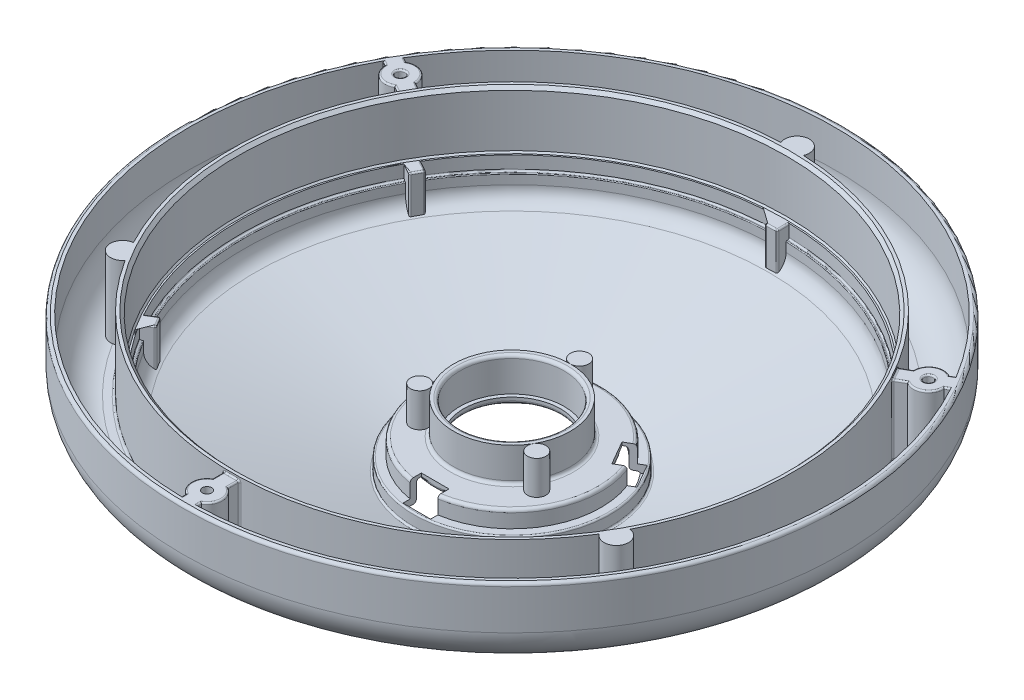
SolidWorks part; units mm, degrees
ref_plane "Front Plane" through (0, 0, 0) normal (0, 0, 1) x (1, 0, 0)
ref_plane "Top Plane" through (0, 0, 0) normal (0, 1, 0) x (1, 0, 0)
ref_plane "Right Plane" through (0, 0, 0) normal (1, 0, 0) x (0, 0, -1)
sketch "Sketch1" plane through (0, 0, 0) normal (0, 0, 1) x (1, 0, 0)
  line L0 (-106.265, 46.5) -> (-105.265, 46.5)
  line L1 (-105.265, 46.5) -> (-105.265, 34.5)
  line L2 (-94.265, 23.5) -> (-92.015, 23.5)
  line L3 (-91.265, 24.25) -> (-91.265, 47.5)
  line L4 (-91.265, 47.5) -> (-90.265, 47.5)
  line L5 (-89.265, 46.5) -> (-89.265, 29.5)
  line L6 (-88.765, 29) -> (-88.265, 29)
  line L7 (-88.265, 29) -> (-88.265, 25)
  line L8 (-87.765, 24.5) -> (-87.515, 24.5)
  line L9 (-87.265, 24.25) -> (-87.265, 21.2906)
  line L11 (-32, 2.6595) -> (-32, 6)
  line L12 (-31.5, 6.5) -> (-29, 6.5)
  line L13 (-29, 6.5) -> (-29, 11)
  line L14 (-28, 12) -> (-20, 12)
  line L15 (-19, 13) -> (-19, 23)
  line L16 (-19, 23) -> (-18, 23)
  line L17 (-17, 22) -> (-17, 12)
  line L18 (-17, 12) -> (-15.75, 12)
  line L19 (-15.75, 12) -> (-15.75, 11)
  line L21 (-27, 10) -> (-27, 5.5)
  line L22 (-28, 4.5) -> (-28.8583, 4.5)
  line L23 (-107.265, 45.5) -> (-107.265, 32.5)
  line L24 (-96.265, 21.5) -> (-91.765, 21.5)
  line L25 (-29.8583, 3.5) -> (-29.8583, 0.6318)
  line L26 (-32.635, 2.1781) -> (-83.6152, 16.4764)
  line L28 (-26, 11) -> (-25.5, 11)
  line L29 (-16.75, 10) -> (-24.75, 10)
  line L30 (-25, 10.25) -> (-25, 10.5)
  line L31 (-91.265, 21) -> (-91.265, 18.4569)
  line L34 (-91.265, 14.5) -> (-29.8583, 0) construction
  line L35 (-87.265, 17.5) -> (-32, 2)
  line L36 (-87.4141, 13.5907) -> (-30.4732, 0.1452)
  line L37 (0, 0) -> (0, 67.3301) construction
  line L38 (-90.265, 47.5) -> (-89.265, 46.5)
  line L39 (-89.265, 29.5) -> (-88.765, 29)
  arc A0 (-28.8583, 4.5) -> (-29.8583, 3.5) centre (-28.8583, 3.5) ccw
  arc A1 (-27, 5.5) -> (-28, 4.5) centre (-28, 5.5) cw
  arc A2 (-26, 11) -> (-27, 10) centre (-26, 10) ccw
  arc A3 (-15.75, 11) -> (-16.75, 10) centre (-16.75, 11) cw
  arc A4 (-18, 23) -> (-17, 22) centre (-18, 22) cw
  arc A5 (-29, 11) -> (-28, 12) centre (-28, 11) cw
  arc A6 (-106.265, 46.5) -> (-107.265, 45.5) centre (-106.265, 45.5) ccw
  arc A7 (-25.5, 11) -> (-25, 10.5) centre (-25.5, 10.5) cw
  arc A8 (-24.75, 10) -> (-25, 10.25) centre (-24.75, 10.25) cw
  arc A9 (-20, 12) -> (-19, 13) centre (-20, 13) ccw
  arc A10 (-32, 6) -> (-31.5, 6.5) centre (-31.5, 6) cw
  arc A11 (-92.015, 23.5) -> (-91.265, 24.25) centre (-92.015, 24.25) ccw
  arc A12 (-88.265, 25) -> (-87.765, 24.5) centre (-87.765, 25) ccw
  arc A13 (-87.515, 24.5) -> (-87.265, 24.25) centre (-87.515, 24.25) cw
  arc A14 (-32, 2.6595) -> (-32.635, 2.1781) centre (-32.5, 2.6595) cw
  arc A15 (-29.8583, 0.6318) -> (-30.4732, 0.1452) centre (-30.3583, 0.6318) cw
  arc A16 (-87.265, 21.2906) -> (-83.6152, 16.4764) centre (-82.265, 21.2906) ccw
  arc A17 (-91.265, 18.4569) -> (-87.4141, 13.5907) centre (-86.265, 18.4569) ccw
  arc A18 (-107.265, 32.5) -> (-96.265, 21.5) centre (-96.265, 32.5) ccw
  arc A19 (-105.265, 34.5) -> (-94.265, 23.5) centre (-94.265, 34.5) ccw
  arc A20 (-91.765, 21.5) -> (-91.265, 21) centre (-91.765, 21) cw
  point P2 (-93.14, 23.5)
  point P6 (-89.265, 47.5)
  point P7 (-89.265, 29)
  point P31 (-28.4291, 4.5)
  point P39 (-27, 4.5)
  point P42 (-27, 11)
  point P45 (-15.75, 10)
  point P48 (-17, 23)
  point P53 (-107.265, 46.5)
  point P56 (-25, 11)
  point P59 (-25, 10)
  point P62 (-19, 12)
  point P65 (-32, 6.5)
  point P70 (-91.265, 23.5)
  point P75 (-88.265, 24.5)
  point P78 (-87.265, 24.5)
  point P93 (-107.265, 21.5)
  point P98 (-91.265, 21.5)
  dimension "D28" = 4
  dimension "D33" = 1
  dimension "D34" = 0.5
  dimension "D35" = 0.25
  dimension "D36" = 1
  dimension "D39" = 0.5
  dimension "D40" = 0.75
  dimension "D41" = 0.5
  dimension "D43" = 0.25
  dimension "D45" = 0.5
  dimension "D46" = 5
  dimension "D47" = 11
  dimension "D48" = 0.5
  dimension "D1" = 14
  dimension "D2" = 2
  dimension "D3" = 2
  dimension "D4" = 2
  dimension "D5" = 107.265
  dimension "D6" = 46.5
  dimension "D7" = 25
  dimension "D8" = 18.5
  dimension "D9" = 1
  dimension "D10" = 1
  dimension "D11" = 4.5
  dimension "D12" = 7
  dimension "D13" = 32
  dimension "D14" = 7
  dimension "D15" = 2
  dimension "D16" = 2
  dimension "D17" = 6.5
  dimension "D18" = 2
  dimension "D19" = 0
  dimension "D20" = 12
  dimension "D21" = 11
  dimension "D22" = 2
  dimension "D23" = 4.5
  dimension "D24" = 15.75
  dimension "D25" = 11
  dimension "D26" = 17
  dimension "D27" = 29
  dimension "D29" = 2
  dimension "D30" = 9.25
  dimension "D31" = 2
  dimension "D32" = 3
  dimension "D37" = 2.381
  dimension "D38" = 24
revolve "Revolve1" add sketch "Sketch1" angle 360 about L37 region at (-105.765, 45.4695, 0)
sketch "Sketch2" plane through (0, 12, 0) normal (0, 1, 0) x (1, 0, 0)
  line L0 (0, 0) -> (0, 135.3376) construction
  line L1 (0, 0) -> (171.5153, -99.0244) construction
  line L2 (0, 0) -> (-123.0376, -71.0358) construction
  line L3 (0, 19) -> (0, 22) construction
  circle A0 centre (0, 0) radius 19 construction
  circle A1 centre (0, 0) radius 19 construction
  circle A2 centre (0, 22) radius 3
  circle A3 centre (19.0526, -11) radius 3
  circle A4 centre (-19.0526, -11) radius 3
  point P19 (0, 0)
  dimension "D4" = 3
  dimension "D1" = 120
  dimension "D2" = 120
  dimension "D3" = 3
extrude "Boss-Extrude3" add sketch "Sketch2" along normal blind 11 separate body
sketch "Sketch3" plane through (0, 23.5, 0) normal (0, 1, 0) x (1, 0, 0)
  line L0 (0, 0) -> (19.0526, -11) construction
  line L1 (19.0526, -11) -> (95.0819, -54.8956) construction
  line L2 (76.8727, -44.3825) -> (80.3368, -46.3825)
  circle A0 centre (0, 0) radius 88.765 construction
  circle A1 centre (0, 0) radius 88.765
  arc A2 (77.135, -48.78) -> (80.8123, -42.4109) centre (80.3368, -46.3825) ccw
  circle A3 centre (0, 0) radius 91.265 construction
  arc A4 (77.135, -48.78) -> (80.8123, -42.4109) centre (0, 0) ccw
  arc A5 (-80.8123, -42.4109) -> (-77.135, -48.78) centre (0, 0) ccw
  arc A6 (-80.8123, -42.4109) -> (-77.135, -48.78) centre (-80.3368, -46.3825) ccw
  arc A7 (3.6773, 91.1909) -> (-3.6773, 91.1909) centre (0, 0) ccw
  arc A8 (3.6773, 91.1909) -> (-3.6773, 91.1909) centre (0, 92.765) ccw
  point P23 (0, 0)
  circle M5 centre (0, 0) radius 92.015
  circle M6 centre (0, 0) radius 94.265
  dimension "D2" = 4
  dimension "D1" = 4
  dimension "D3" = 3
extrude "Boss-Extrude4" add sketch "Sketch3" along normal through all contours A2 M6 | A2 M6 M5 | A4 L2 A2 M5 | A4 A2 L2 M5 | A6 M6 | A6 M6 M5 | A6 A5 M5 | A8 M5 M6 | A8 A7 region at (80.2954, 23.5, 44.1591) region at (78.3906, 23.5, 47.4583) region at (80.6305, 23.5, 46.5521) region at (82.5181, 23.5, 47.6418) region at (-79.343, 23.5, 45.8087) region at (-80.6305, 23.5, 46.5521) region at (-82.5181, 23.5, 47.6418) region at (0, 23.5, -93.1041)
sketch "Sketch6" plane through (0, 29, 0) normal (0, 1, 0) x (1, 0, 0)
  line L0 (0, 0) -> (19.0526, -11) construction
  line L1 (19.0526, -11) -> (112.9006, -65.1832) construction
  line L2 (76.4397, -44.1325) -> (74.7077, -43.1325) construction
  line L3 (71.9943, -43.9308) -> (75.506, -45.8459)
  line L4 (71.9943, -43.9308) -> (73.9093, -40.4191)
  line L5 (75.506, -45.8459) -> (77.4211, -42.3342)
  line L6 (73.9093, -40.4191) -> (77.4211, -42.3342)
  line L7 (71.9943, -43.9308) -> (77.4211, -42.3342) construction
  line L8 (75.506, -45.8459) -> (73.9093, -40.4191) construction
  line L9 (-2.0481, -84.3143) -> (-1.9507, -88.3131)
  line L10 (-2.0481, -84.3143) -> (1.9507, -84.2169)
  line L11 (1.9507, -84.2169) -> (2.0481, -88.2157)
  line L12 (-1.9507, -88.3131) -> (2.0481, -88.2157)
  line L13 (-74.0423, -40.3834) -> (-77.4567, -42.4672)
  line L14 (-74.0423, -40.3834) -> (-71.9586, -43.7978)
  line L15 (-71.9586, -43.7978) -> (-75.373, -45.8816)
  line L16 (-77.4567, -42.4672) -> (-75.373, -45.8816)
  line L17 (-71.9943, 43.9308) -> (-75.506, 45.8459)
  line L18 (-71.9943, 43.9308) -> (-73.9093, 40.4191)
  line L19 (-73.9093, 40.4191) -> (-77.4211, 42.3342)
  line L20 (-75.506, 45.8459) -> (-77.4211, 42.3342)
  line L21 (2.0481, 84.3143) -> (1.9507, 88.3131)
  line L22 (2.0481, 84.3143) -> (-1.9507, 84.2169)
  line L23 (-1.9507, 84.2169) -> (-2.0481, 88.2157)
  line L24 (1.9507, 88.3131) -> (-2.0481, 88.2157)
  line L25 (74.0423, 40.3834) -> (77.4567, 42.4672)
  line L26 (74.0423, 40.3834) -> (71.9586, 43.7978)
  line L27 (71.9586, 43.7978) -> (75.373, 45.8816)
  line L28 (77.4567, 42.4672) -> (75.373, 45.8816)
  circle A0 centre (0, 0) radius 88.265 construction
  point P36 (0, 0)
  dimension "D1" = 2
  dimension "D2" = 4
  dimension "D3" = 4
  dimension "D4" = 88.2394
  dimension "D5" = 6
extrude "Boss-Extrude6" add sketch "Sketch6" against normal up to next
fillet "Fillet1" radius 0.5 30 edges at (2.0003, 29, -86.2788) (2.0481, 22.8706, -84.3143) (0.0487, 29, -84.2656) (-1.9507, 22.8485, -84.2169) (-1.9994, 29, -86.2163) (75.7198, 29, -41.4071) (74.0423, 22.8706, -40.3834) (73.0005, 29, -42.0906) (71.9586, 22.8485, -43.7978) (73.6658, 29, -44.8397) (73.7195, 29, 44.8717) (71.9943, 22.8706, 43.9308) (73.9093, 22.8485, 40.4191) (75.6652, 29, 41.3766) (72.9518, 29, 42.175) (-2.0481, 22.8706, 84.3143) (-2.0003, 29, 86.2788) (-0.0487, 29, 84.2656) (1.9507, 22.8485, 84.2169) (1.9994, 29, 86.2163) (-74.0423, 22.8706, 40.3834) (-75.7198, 29, 41.4071) (-71.9586, 22.8485, 43.7978) (-73.0005, 29, 42.0906) (-73.6658, 29, 44.8397) (-73.7195, 29, -44.8717) (-75.6652, 29, -41.3766) (-71.9943, 22.8706, -43.9308) (-73.9093, 22.8485, -40.4191) (-72.9518, 29, -42.175)
sketch "Sketch8" plane through (0, 46.5, 0) normal (0, 1, 0) x (1, 0, 0)
  line L0 (0, 0) -> (19.0526, -11) construction
  line L1 (19.0526, -11) -> (114.5131, -66.1142) construction
  line L2 (0, 0) -> (0, -134.6557) construction
  line L3 (-2.5, -91.2308) -> (-2.5, -94.9349)
  line L4 (2.5, 0) -> (2.5, -1.4434)
  line L5 (0, -91.265) -> (0, -105.265) construction
  line L6 (2.5, -91.2308) -> (2.5, -94.9349)
  line L7 (2.5, -103.5951) -> (2.5, -105.2353)
  line L8 (2.5, 0) -> (2.5, -134.6557) construction
  line L9 (-2.5, 0) -> (-2.5, -134.6557) construction
  line L10 (-2.5, -103.5951) -> (-2.5, -105.2353)
  line L11 (-90.966, 49.6325) -> (-92.3865, 50.4526)
  line L12 (-88.466, 53.9626) -> (-89.8865, 54.7827)
  line L13 (-77.7581, 47.7804) -> (-80.966, 49.6325)
  line L14 (-80.2581, 43.4503) -> (-83.466, 45.3024)
  line L15 (88.466, 53.9626) -> (89.8865, 54.7827)
  line L16 (90.966, 49.6325) -> (92.3865, 50.4526)
  line L17 (80.2581, 43.4503) -> (83.466, 45.3024)
  line L18 (77.7581, 47.7804) -> (80.966, 49.6325)
  arc A0 (-77.135, -48.78) -> (77.135, -48.78) centre (0, 0) ccw construction
  arc A1 (-2.5, -91.2308) -> (2.5, -91.2308) centre (0, 0) ccw
  circle A2 centre (0, 0) radius 105.265 construction
  arc A3 (-2.5, -105.2353) -> (2.5, -105.2353) centre (0, 0) ccw
  arc A4 (2.5, -103.5951) -> (2.5, -94.9349) centre (0, -99.265) ccw
  circle A5 centre (0, -99.265) radius 1.5
  arc A6 (-2.5, -94.9349) -> (-2.5, -103.5951) centre (0, -99.265) ccw
  arc A7 (-89.8865, 54.7827) -> (-92.3865, 50.4526) centre (0, 0) ccw
  arc A8 (-80.966, 49.6325) -> (-88.466, 53.9626) centre (-85.966, 49.6325) ccw
  arc A9 (-77.7581, 47.7804) -> (-80.2581, 43.4503) centre (0, 0) ccw
  arc A10 (-90.966, 49.6325) -> (-83.466, 45.3024) centre (-85.966, 49.6325) ccw
  circle A11 centre (-85.966, 49.6325) radius 1.5
  arc A12 (92.3865, 50.4526) -> (89.8865, 54.7827) centre (0, 0) ccw
  arc A13 (83.466, 45.3024) -> (90.966, 49.6325) centre (85.966, 49.6325) ccw
  arc A14 (80.2581, 43.4503) -> (77.7581, 47.7804) centre (0, 0) ccw
  arc A15 (88.466, 53.9626) -> (80.966, 49.6325) centre (85.966, 49.6325) ccw
  circle A16 centre (85.966, 49.6325) radius 1.5
  point P51 (0, 0)
  circle M13 centre (0, 0) radius 105.265
  dimension "D2" = 2.5
  dimension "D4" = 10
  dimension "D5" = 3
  dimension "D1" = 60
  dimension "D6" = 6
  dimension "D3" = 2.5
  dimension "D7" = 3
extrude "Boss-Extrude7" add sketch "Sketch8" against normal up to next contours L3 A6 L10 L7 A4 L6 A1 A5 M13 | L15 A15 L18 A14 L17 A13 L16 A16 M13 | L11 A10 L14 A9 L13 A8 L12 A11 M13 region at (0, 46.5, 91.4373) region at (-91.0019, 46.5, -52.54) region at (91.5837, 46.5, -50.2028)
fillet "Fillet2" radius 0.5 47 edges at (79.3825, 23.5, -48.7183) (2.5, 23.5, 93.1064) (-79.3825, 23.5, -48.7183) (77.9461, 23.7224, -47.889) (2.5, 24.7495, 92.5407) (-77.9461, 23.7224, -47.889) (77.7581, 35.375, -47.7804) (2.5, 35.375, 91.2308) (-77.7581, 35.375, -47.7804) (79.0378, 46.5, -45.6325) (0, 46.5, 91.265) (-79.0378, 46.5, -45.6325) (81.8825, 23.5, -44.3882) (80.4461, 23.7224, -43.5588) (-2.5, 23.5, 93.1064) (-2.5, 24.7495, 92.5407) (-81.8825, 23.5, -44.3882) (-80.4461, 23.7224, -43.5588) (80.2581, 35.375, -43.4503) (89.1762, 46.5, -54.3727) (79.3621, 46.5, -48.7065) (83.466, 46.5, -53.9626) (91.6762, 46.5, -50.0425) (81.8621, 46.5, -44.3763) (88.466, 46.5, -45.3024) (85.966, 46.5, -48.1325) (-85.966, 46.5, -48.1325) (-2.5, 35.375, 91.2308) (-2.5, 46.5, 104.4152) (-2.5, 46.5, 93.0828) (-5, 46.5, 99.265) (2.5, 46.5, 93.0828) (2.5, 46.5, 104.4152) (5, 46.5, 99.265) (-80.2581, 35.375, -43.4503) (-91.6762, 46.5, -50.0425) (-89.1762, 46.5, -54.3727) (-79.3621, 46.5, -48.7065) (-83.466, 46.5, -53.9626) (-81.8621, 46.5, -44.3763) (-88.466, 46.5, -45.3024)
sketch "Sketch9" plane through (0, 12, 0) normal (0, 1, 0) x (1, 0, 0)
  line L0 (0, 0) -> (19.0526, -11) construction
  line L1 (19.0526, -11) -> (137.0771, -79.1415) construction
  line L2 (0, 0) -> (111.6243, 64.4463) construction
  line L3 (19.4006, 16.3971) -> (24.5968, 19.3971)
  line L4 (19.4006, 16.3971) -> (23.9006, 8.6029)
  line L5 (24.5968, 19.3971) -> (29.0968, 11.6029)
  line L6 (23.9006, 8.6029) -> (29.0968, 11.6029)
  line L7 (19.4006, 16.3971) -> (29.0968, 11.6029) construction
  line L8 (24.5968, 19.3971) -> (23.9006, 8.6029) construction
  line L9 (4.5, -25) -> (4.5, -31)
  line L10 (4.5, -25) -> (-4.5, -25)
  line L11 (-4.5, -25) -> (-4.5, -31)
  line L12 (4.5, -31) -> (-4.5, -31)
  line L13 (-23.9006, 8.6029) -> (-29.0968, 11.6029)
  line L14 (-23.9006, 8.6029) -> (-19.4006, 16.3971)
  line L15 (-19.4006, 16.3971) -> (-24.5968, 19.3971)
  line L16 (-29.0968, 11.6029) -> (-24.5968, 19.3971)
  circle A0 centre (0, 0) radius 28 construction
  circle A1 centre (0, 0) radius 28
  point P9 (24.2487, 14)
  point P11 (24.2487, 14)
  point P26 (0, 0)
  circle M7 centre (0, 0) radius 28
  dimension "D1" = 60
  dimension "D2" = 9
  dimension "D3" = 6
  dimension "D4" = 0
  dimension "D5" = 3
extrude "Cut-Extrude1" cut sketch "Sketch9" against normal blind 8 contours L6 L5 L3 M7 | L4 L6 L3 M7 | L14 L15 L13 M7 | L16 L13 L15 M7 | L10 L11 L9 M7 | L12 L9 L11 M7 region at (22.899, 12, -13.2208) region at (25.4937, 12, -14.7188) region at (-25.4937, 12, -14.7188) region at (-22.899, 12, -13.2208) region at (0, 12, 26.4415) region at (0, 12, 29.4376)
